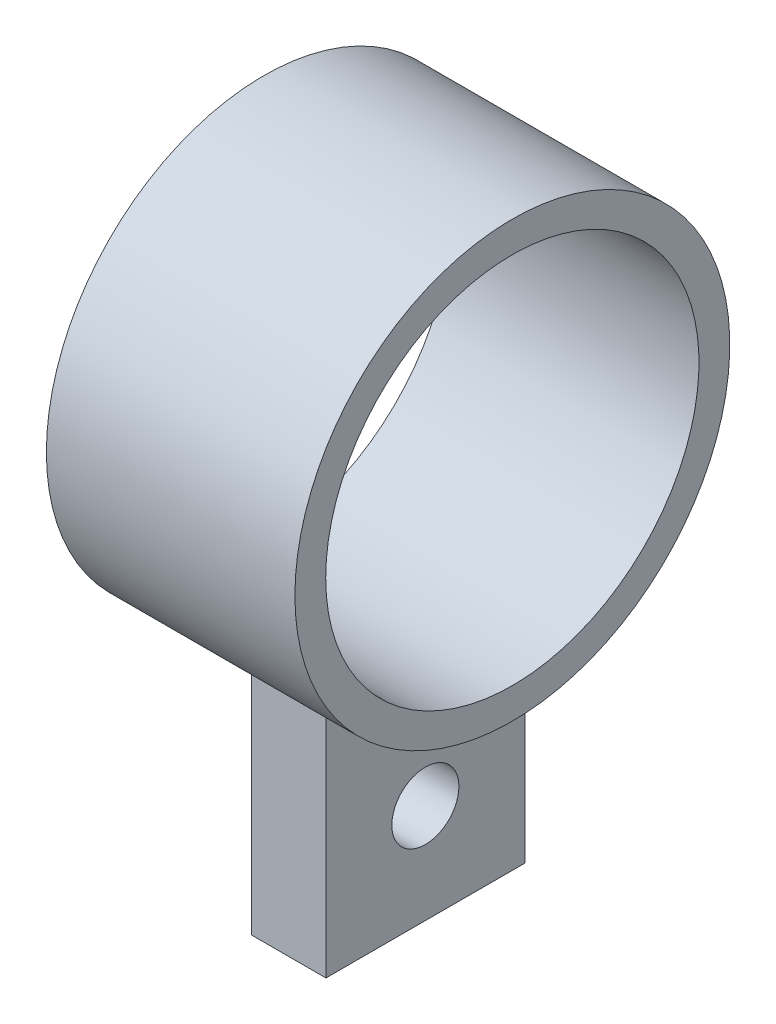
SolidWorks part; units mm, degrees
ref_plane "Front Plane" through (0, 0, 0) normal (0, 0, 1) x (1, 0, 0)
ref_plane "Top Plane" through (0, 0, 0) normal (0, 1, 0) x (1, 0, 0)
ref_plane "Right Plane" through (0, 0, 0) normal (1, 0, 0) x (0, 0, -1)
sketch "Collar Sketch" plane through (0, 0, 0) normal (0, 0, 1) x (1, 0, 0)
  line L0 (-3000, 0) -> (3000, 0) construction
  line L1 (232.6352, 15.02) -> (252.6352, 15.02)
  line L2 (252.6352, 15.02) -> (252.6352, 17.5)
  line L3 (252.6352, 17.5) -> (232.6352, 17.5)
  line L4 (232.6352, 17.5) -> (232.6352, 15.02)
revolve "Collar" add sketch "Collar Sketch" angle 360 about L0
ref_axis "Engine Axis" through (253.6352, 0, 0) along (-1, 0, 0)
sketch "Tab Sketch" plane through (0, 0, 0) normal (0, 0, 1) x (1, 0, 0)
  line L0 (239.6352, -34.8967) -> (245.6352, -34.8967)
  line L1 (245.6352, -34.8967) -> (245.6352, -8)
  line L2 (245.6352, -8) -> (239.6352, -8)
  line L3 (239.6352, -8) -> (239.6352, -34.8967)
extrude "Tab" add sketch "Tab Sketch" along normal mid plane 16
sketch "Tube Clearance Sketch" plane through (0, 0, 0) normal (0, 0, 1) x (1, 0, 0)
  line L0 (-3000, 0) -> (3000, 0) construction
  line L1 (238.6352, 0) -> (246.6352, 0)
  line L2 (246.6352, 0) -> (246.6352, 15.02)
  line L3 (246.6352, 15.02) -> (238.6352, 15.02)
  line L4 (238.6352, 15.02) -> (238.6352, 0)
revolve "Tube Clearance" cut sketch "Tube Clearance Sketch" angle 360 about L0
ref_plane "Hole Plane" through (239.6352, 0, 0) normal (1, 0, 0) x (0, 0, -1)
sketch "Pin Hole Sketch" plane through (239.6352, 0, 0) normal (1, 0, 0) x (0, 0, -1)
  circle A0 centre (0, -26.8967) radius 2.7
extrude "Pin Hole" cut sketch "Pin Hole Sketch" along normal blind 6
